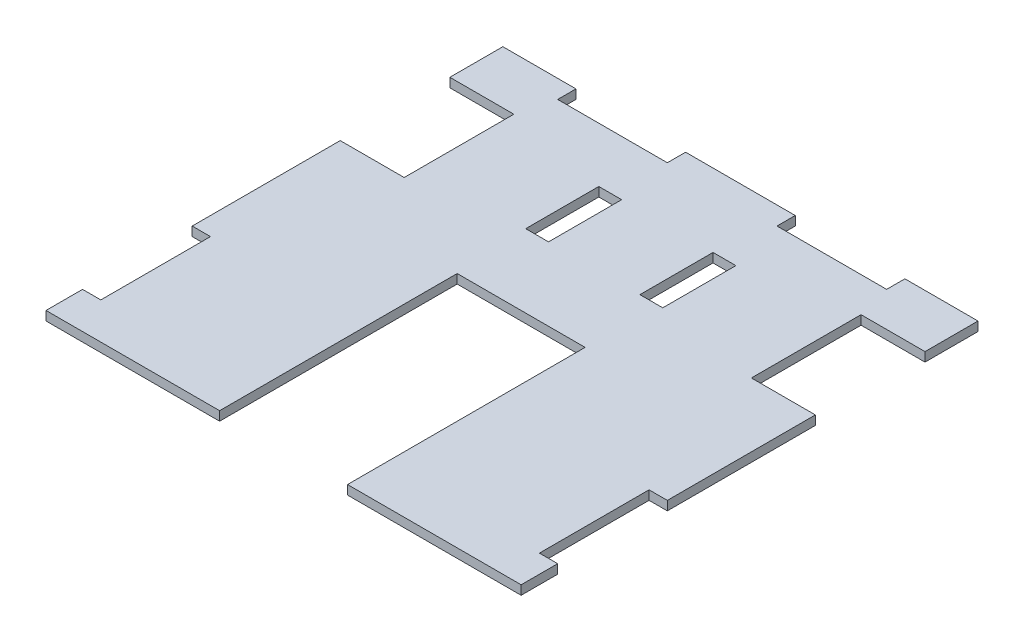
SolidWorks part; units mm, degrees
material "7050-T73510"
ref_plane "Front Plane" through (0, 0, 0) normal (0, 0, 1) x (1, 0, 0)
ref_plane "Top Plane" through (0, 0, 0) normal (0, 1, 0) x (1, 0, 0)
ref_plane "Right Plane" through (0, 0, 0) normal (1, 0, 0) x (0, 0, -1)
sketch "Sketch1" plane through (0, 0, 0) normal (0, 1, 0) x (1, 0, 0)
  line L0 (0, -55) -> (0, 55) construction
  line L1 (-165.1, -76.2) -> (165.1, -76.2)
  line L2 (-165.1, -76.2) -> (-165.1, 76.2)
  line L3 (-165.1, 76.2) -> (165.1, 76.2)
  line L4 (165.1, -76.2) -> (165.1, 76.2)
  line L5 (-165.1, -76.2) -> (165.1, 76.2) construction
  line L6 (-165.1, 76.2) -> (165.1, -76.2) construction
  line L7 (-165.1, -76.2) -> (-31.75, -76.2)
  line L8 (-165.1, -76.2) -> (-165.1, -241.3)
  line L9 (-165.1, -241.3) -> (-31.75, -241.3)
  line L10 (-31.75, -76.2) -> (-31.75, -241.3)
  line L11 (31.75, -76.2) -> (31.75, -241.3)
  line L12 (165.1, -241.3) -> (31.75, -241.3)
  line L13 (165.1, -76.2) -> (165.1, -241.3)
  line L14 (165.1, -76.2) -> (31.75, -76.2)
  line L15 (-44.45, -76.2) -> (-44.45, -241.3)
  line L16 (44.45, -76.2) -> (44.45, -241.3)
  point P0 (0, 0)
  dimension "D1" = 330.2
  dimension "D2" = 152.4
  dimension "D3" = 317.5
  dimension "D4" = 63.5
  dimension "D5" = 12.7
extrude "Boss-Extrude1" add sketch "Sketch1" along normal blind 6.35 contours L15 L1 L8 L9 | L14 L16 L12 L13 | L1 L7 L14 L4 L3 L2 region at (0, 0, 0) region at (-104.775, 0, 158.75) region at (104.775, 0, 158.75)
sketch "Sketch2" plane through (0, 6.35, 0) normal (0, 1, 0) x (1, 0, 0)
  line L0 (165.1, -241.3) -> (165.1, 76.2) construction
  line L1 (165.1, 39.37) -> (120.65, 39.37)
  line L2 (165.1, 39.37) -> (165.1, -36.83)
  line L3 (165.1, -36.83) -> (120.65, -36.83)
  line L4 (120.65, 39.37) -> (120.65, -36.83)
  line L5 (-165.1, 76.2) -> (165.1, 76.2) construction
  line L6 (165.1, -139.7) -> (152.4, -139.7)
  line L7 (165.1, -139.7) -> (165.1, -215.9)
  line L8 (165.1, -215.9) -> (152.4, -215.9)
  line L9 (152.4, -139.7) -> (152.4, -215.9)
  line L10 (0, -55) -> (0, 55) construction
  line L11 (-165.1, -215.9) -> (-152.4, -215.9)
  line L12 (-152.4, -139.7) -> (-152.4, -215.9)
  line L13 (-165.1, -139.7) -> (-152.4, -139.7)
  line L14 (-165.1, -139.7) -> (-165.1, -215.9)
  line L15 (-165.1, -36.83) -> (-120.65, -36.83)
  line L16 (-120.65, 39.37) -> (-120.65, -36.83)
  line L17 (-165.1, 39.37) -> (-120.65, 39.37)
  line L18 (-165.1, 39.37) -> (-165.1, -36.83)
  line L19 (-114.3, 63.5) -> (-38.1, 63.5)
  line L20 (114.3, 76.2) -> (38.1, 76.2)
  line L21 (114.3, 76.2) -> (114.3, 63.5)
  line L22 (114.3, 63.5) -> (38.1, 63.5)
  line L23 (38.1, 76.2) -> (38.1, 63.5)
  line L24 (-38.1, 76.2) -> (-38.1, 63.5)
  line L25 (-114.3, 76.2) -> (-38.1, 76.2)
  line L26 (-114.3, 76.2) -> (-114.3, 63.5)
  dimension "D1" = 44.45
  dimension "D2" = 12.7
  dimension "D3" = 76.2
  dimension "D4" = 76.2
  dimension "D5" = 36.83
  dimension "D6" = 215.9
  dimension "D7" = 76.2
  dimension "D8" = 12.7
  dimension "D9" = 76.2
extrude "Cut-Extrude1" cut sketch "Sketch2" against normal through all
sketch "Sketch3" plane through (0, 6.35, 0) normal (0, 1, 0) x (1, 0, 0)
  line L0 (-44.45, -76.2) -> (44.45, -76.2) construction
  line L1 (-47.625, -25.4) -> (-31.75, -25.4)
  line L2 (-47.625, -25.4) -> (-47.625, 25.4)
  line L3 (-47.625, 25.4) -> (-31.75, 25.4)
  line L4 (-31.75, -25.4) -> (-31.75, 25.4)
  line L5 (0, -3.4925) -> (0, 3.4925) construction
  line L6 (47.625, 25.4) -> (31.75, 25.4)
  line L7 (31.75, -25.4) -> (31.75, 25.4)
  line L8 (47.625, -25.4) -> (31.75, -25.4)
  line L9 (47.625, -25.4) -> (47.625, 25.4)
  dimension "D1" = 50.8
  dimension "D2" = 15.875
  dimension "D3" = 50.8
  dimension "D4" = 63.5
extrude "Cut-Extrude2" cut sketch "Sketch3" against normal through all
